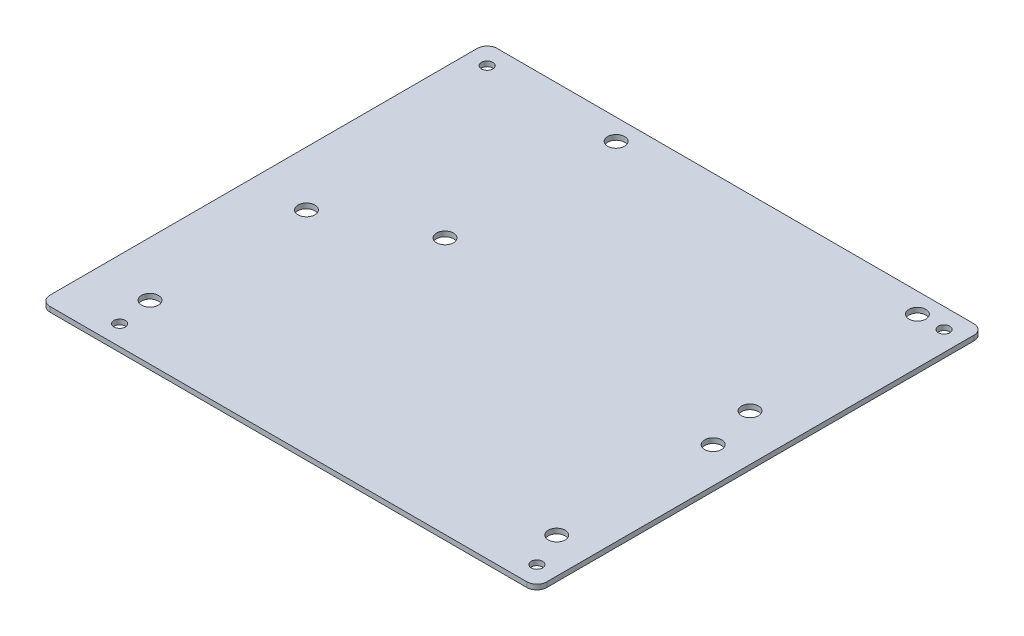
SolidWorks part; units mm, degrees
ref_plane "Front Plane" through (0, 0, 0) normal (0, 0, 1) x (1, 0, 0)
ref_plane "Top Plane" through (0, 0, 0) normal (0, 1, 0) x (1, 0, 0)
ref_plane "Right Plane" through (0, 0, 0) normal (1, 0, 0) x (0, 0, -1)
sketch "Sketch1" plane through (0, 0, 0) normal (0, 1, 0) x (1, 0, 0)
  line L1 (0, 0) -> (158.75, 0)
  line L2 (0, 0) -> (0, 142.875)
  line L4 (158.75, 0) -> (158.75, 142.875)
  line L19 (158.75, 142.875) -> (0, 142.875)
  line L21 (351.9786, 184.7613) -> (351.9786, -3.4747) construction
  dimension "D1" = 142.875
  dimension "D2" = 351.9786
  dimension "D5" = 158.75
extrude "Boss-Extrude1" add sketch "Sketch1" along normal blind 1.6002 contours L1 L19 L4 L2 region at (79.375, 0, -71.4375)
fillet "Fillet1" radius 3.175 4 edges at (158.75, 0.8001, 0) (0, 0.8001, -142.875) (158.75, 0.8001, -142.875) (0, 0.8001, 0)
sketch "Sketch2" plane through (0, 1.6002, 0) normal (0, 1, 0) x (1, 0, 0)
  line L0 (3.175, 139.7) -> (155.575, 3.175) construction
  line L1 (0, 3.175) -> (0, 139.7) construction
  line L2 (152.4, 136.525) -> (6.35, 136.525) construction
  line L3 (152.4, 136.525) -> (152.4, 6.35) construction
  line L4 (152.4, 6.35) -> (6.35, 6.35) construction
  line L5 (6.35, 136.525) -> (6.35, 6.35) construction
  line L6 (152.4, 136.525) -> (6.35, 6.35) construction
  line L7 (152.4, 6.35) -> (6.35, 136.525) construction
  line L8 (155.575, 142.875) -> (3.175, 142.875) construction
  circle A0 centre (6.35, 136.525) radius 1.8288
  circle A1 centre (152.4, 136.525) radius 1.8288
  circle A2 centre (152.4, 6.35) radius 1.8288
  circle A4 centre (19.05, 6.35) radius 1.8288
  point P2 (79.375, 71.4375)
  dimension "D3" = 3.6576
  dimension "D4" = 19.05
  dimension "D1" = 6.35
  dimension "D2" = 6.35
extrude "Cut-Extrude1" cut sketch "Sketch2" against normal through all
sketch "Sketch5" plane through (0, 1.6002, 0) normal (0, 1, 0) x (1, 0, 0)
  circle A0 centre (47.93, 136.175) radius 2.7051
  circle A1 centre (143.912, 136.475) radius 2.7051
  circle A2 centre (47.295, 82.098) radius 2.7051
  circle A3 centre (143.912, 82.987) radius 2.7051
  circle A4 centre (17.4, 67.7) radius 2.7051
  circle A5 centre (147.382, 67.721) radius 2.7051
  circle A6 centre (147.4, 17.7) radius 2.7051
  circle A7 centre (17.4, 17.7) radius 2.7051
  dimension "D1" = 5.4102
extrude "Cut-Extrude2" cut sketch "Sketch5" against normal through all
